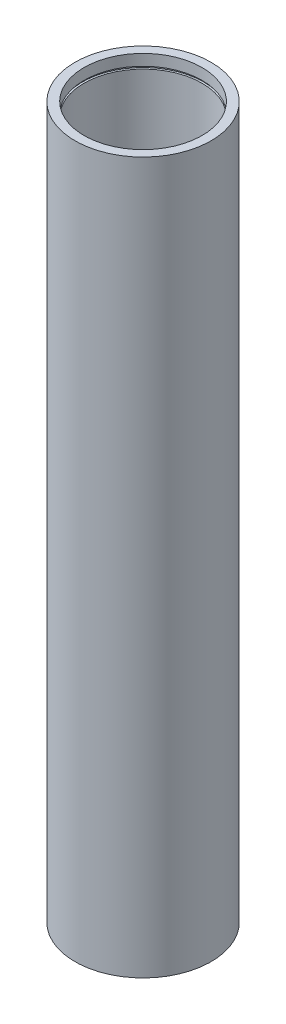
SolidWorks part; units mm, degrees
material "1060 Alloy"
ref_plane "Front Plane" through (0, 0, 0) normal (0, 0, 1) x (1, 0, 0)
ref_plane "Top Plane" through (0, 0, 0) normal (0, 1, 0) x (1, 0, 0)
ref_plane "Right Plane" through (0, 0, 0) normal (1, 0, 0) x (0, 0, -1)
sketch "Sketch2" plane through (0, 0, 0) normal (0, 0, 1) x (1, 0, 0)
  line L0 (0, 0) -> (0, 365.76)
  line L1 (41.275, 11.2522) -> (42.5958, 11.2522)
  line L2 (42.5958, 11.2522) -> (42.5958, 9.525)
  line L3 (41.275, 0) -> (47.625, 0)
  line L4 (41.275, 497.5098) -> (41.275, 489.712)
  line L5 (41.275, 497.5098) -> (47.625, 497.5098)
  line L6 (47.625, 0) -> (47.625, 497.5098)
  line L7 (42.5958, 9.525) -> (41.275, 9.525)
  line L8 (41.275, 487.9848) -> (42.5958, 487.9848)
  line L9 (42.5958, 487.9848) -> (42.5958, 489.712)
  line L10 (42.5958, 489.712) -> (41.275, 489.712)
  line L11 (41.275, 487.9848) -> (41.275, 11.2522)
  line L12 (41.275, 11.2522) -> (41.2565, 11.2265)
  line L13 (41.275, 9.525) -> (41.275, 0)
  dimension "D1" = 365.76
  dimension "D2" = 41.275
  dimension "D3" = 6.35
  dimension "D4" = 497.5098
  dimension "D5" = 9.525
  dimension "D6" = 1.7272
  dimension "D7" = 1.3208
  dimension "D8" = 9.525
  dimension "D9" = 1.3208
  dimension "D10" = 1.7272
revolve "Revolve1" add sketch "Sketch2" angle 360 about L0 region at (44.4536, 248.7537, 0)
